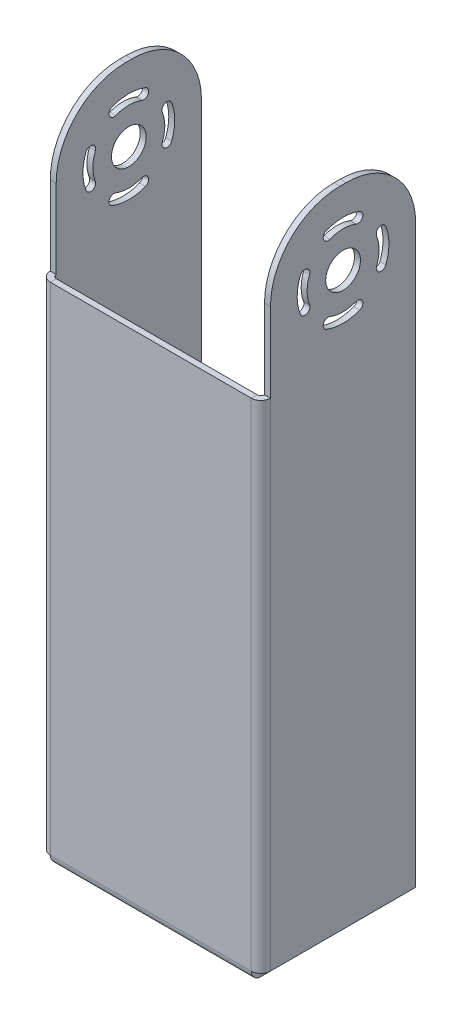
SolidWorks part; units mm, degrees
note: The reader was unsure of these and kept them because the rebuilt part matched: flange length of "邊線-凸緣1", "邊線-凸緣3".
ref_plane "前基準面" through (0, 0, 0) normal (0, 0, 1) x (1, 0, 0)
ref_plane "上基準面" through (0, 0, 0) normal (0, 1, 0) x (1, 0, 0)
ref_plane "右基準面" through (0, 0, 0) normal (1, 0, 0) x (0, 0, -1)
sketch "草圖1" plane through (0, 0, 0) normal (0, 0, 1) x (1, 0, 0)
  line L1 (-49.32, 41.3608) -> (-8.82, 41.3608)
  line L2 (-49.32, 41.3608) -> (-49.32, -58.6392)
  line L3 (-49.32, -58.6392) -> (-8.82, -58.6392)
  line L4 (-8.82, 41.3608) -> (-8.82, -58.6392)
  dimension "D1" = 40.5
  dimension "D2" = 100
base flange "基材-凸緣1" sketch "草圖1" thickness 1.2 reverse thickness direction no parameters "D1"=0.7366
edge flange "邊線-凸緣1" sketch "草圖10" flange profiles "草圖10", "草圖11" flange angle 90 flange length 30 flange position bend outside bend radius 0.7366 thickness 1.2 relief rectangular parameters "D6"=10, "D8"=1
sketch "草圖10" plane through (-8.82, 0, -1.2) normal (-1, 0, 0) x (0, 1, 0)
  line L1 (41.3608, 0) -> (-58.6392, 0) construction
  line L2 (-58.6392, 0) -> (-58.6392, 30)
  line L3 (-58.6392, 30) -> (41.3608, 30)
  line L4 (41.3608, 30) -> (41.3608, 0)
  line L5 (41.3608, 0) -> (-58.6392, 0)
sketch "草圖11" plane through (-49.32, 0, -1.2) normal (1, 0, 0) x (0, -1, 0)
  line L0 (58.6392, 0) -> (-41.3608, 0) construction
  line L1 (58.6392, 0) -> (-41.3608, 0)
  line L2 (58.6392, 0) -> (58.6392, 30)
  line L3 (58.6392, 30) -> (-41.3608, 30)
  line L4 (-41.3608, 30) -> (-41.3608, 0)
bend "邊線彎折7" bend radius 0.7366 bend angle 90 parameters "D5"=1
bend "邊線彎折8" bend radius 0.7366 bend angle 90 parameters "D5"=2
edge flange "邊線-凸緣3" sketch "草圖21" flange angle 90 flange length 20.735 flange position bend outside bend radius 0.7366 thickness 1.2 relief rectangular parameters "D6"=10
sketch "草圖21" plane through (0, -58.6392, -1.2) normal (0, -1, 0) x (-1, 0, 0)
  line L0 (49.32, 0) -> (8.82, 0) construction
  line L1 (49.32, 0) -> (8.82, 0)
  line L2 (8.82, 0) -> (8.82, 20.735)
  line L3 (8.82, 20.735) -> (49.32, 20.735)
  line L4 (49.32, 20.735) -> (49.32, 0)
bend "邊線彎折4" bend radius 0.7366 bend angle 90 parameters "D5"=3
sketch "草圖25" plane through (0, -60.5758, 0) normal (0, -1, 0) x (1, 0, 0)
  line L0 (-29.07, -1.9366) -> (-29.07, -21.935) construction
  line L1 (-49.32, -1.9366) -> (-8.82, -1.9366) construction
  line L2 (-49.32, -11.9358) -> (-8.82, -11.9358) construction
  line L3 (-49.32, -1.9366) -> (-49.32, -21.935) construction
  line L4 (-8.82, -21.935) -> (-8.82, -1.9366) construction
  line L5 (-49.32, -21.935) -> (-8.82, -21.935) construction
  circle A0 centre (-43.58, -6.9366) radius 1.5
  circle A1 centre (-43.58, -16.935) radius 1.5
  circle A2 centre (-14.56, -16.935) radius 1.5
  circle A3 centre (-14.56, -6.9366) radius 1.5
  dimension "D1" = 3
  dimension "D2" = 14.51
  dimension "D3" = 4.9992
  dimension "D4" = 14.51
extrude "除料-伸長1" cut sketch "草圖25" against normal blind 10 normal cut yes
sketch "草圖26" plane through (0, 41.3608, 0) normal (0, 1, 0) x (1, 0, 0)
  line L0 (-51.2566, 31.2) -> (-51.2566, 1.9366) construction
  line L1 (-51.2566, 1.9366) -> (-50.0566, 1.9366) construction
  line L2 (-50.0566, 1.9366) -> (-50.0566, 31.2) construction
  line L3 (-50.0566, 31.2) -> (-51.2566, 31.2) construction
  line L4 (-8.0834, 31.2) -> (-8.0834, 1.9366) construction
  line L5 (-8.0834, 1.9366) -> (-6.8834, 1.9366) construction
  line L6 (-6.8834, 1.9366) -> (-6.8834, 31.2) construction
  line L7 (-6.8834, 31.2) -> (-8.0834, 31.2) construction
  line L8 (-51.2566, 31.2) -> (-51.2566, 1.9366)
  line L9 (-51.2566, 1.9366) -> (-50.0566, 1.9366)
  line L10 (-50.0566, 1.9366) -> (-50.0566, 31.2)
  line L11 (-50.0566, 31.2) -> (-51.2566, 31.2)
  line L12 (-8.0834, 31.2) -> (-8.0834, 1.9366)
  line L13 (-8.0834, 1.9366) -> (-6.8834, 1.9366)
  line L14 (-6.8834, 1.9366) -> (-6.8834, 31.2)
  line L15 (-6.8834, 31.2) -> (-8.0834, 31.2)
extrude "填料-伸長1" add sketch "草圖26" along normal blind 30
sketch "草圖29" plane through (-6.8834, 0, 0) normal (1, 0, 0) x (0, 0, -1)
  line L0 (1.9366, 56.3608) -> (31.2, 56.3608) construction
  line L1 (1.9366, 71.3608) -> (1.9366, 41.3608) construction
  line L2 (31.2, 71.3608) -> (31.2, -58.6392) construction
  line L3 (16.5683, 71.3608) -> (16.5683, 41.3608) construction
  line L4 (1.9366, 71.3608) -> (31.2, 71.3608) construction
  arc A0 (25.1851, 52.9972) -> (25.1851, 59.7244) centre (16.5683, 56.3608) ccw
  arc A1 (25.1851, 59.7244) -> (23.322, 58.9972) centre (24.2535, 59.3608) ccw
  circle A2 centre (16.5683, 56.3608) radius 3.5
  arc A3 (13.2047, 64.9776) -> (13.9319, 63.1145) centre (13.5683, 64.046) ccw
  arc A4 (19.2047, 63.1145) -> (19.9319, 64.9776) centre (19.5683, 64.046) ccw
  arc A5 (19.9319, 64.9776) -> (13.2047, 64.9776) centre (16.5683, 56.3608) ccw
  arc A6 (19.2047, 63.1145) -> (13.9319, 63.1145) centre (16.5683, 56.3608) ccw
  arc A7 (23.322, 53.7244) -> (25.1851, 52.9972) centre (24.2535, 53.3608) ccw
  arc A8 (23.322, 53.7244) -> (23.322, 58.9972) centre (16.5683, 56.3608) ccw
  arc A9 (13.2047, 47.7441) -> (19.9319, 47.7441) centre (16.5683, 56.3608) ccw
  arc A10 (19.9319, 47.7441) -> (19.2047, 49.6071) centre (19.5683, 48.6756) ccw
  arc A11 (13.9319, 49.6071) -> (13.2047, 47.7441) centre (13.5683, 48.6756) ccw
  arc A12 (13.9319, 49.6071) -> (19.2047, 49.6071) centre (16.5683, 56.3608) ccw
  arc A13 (7.9515, 59.7244) -> (7.9515, 52.9972) centre (16.5683, 56.3608) ccw
  arc A14 (7.9515, 52.9972) -> (9.8146, 53.7244) centre (8.8831, 53.3608) ccw
  arc A15 (9.8146, 58.9972) -> (7.9515, 59.7244) centre (8.8831, 59.3608) ccw
  arc A16 (9.8146, 58.9972) -> (9.8146, 53.7244) centre (16.5683, 56.3608) ccw
  point P39 (16.5683, 56.3608)
  dimension "D1" = 4
  dimension "D3" = 7
  dimension "D4" = 2
  dimension "D5" = 2
  dimension "D6" = 6
  dimension "D7" = 3
extrude "除料-伸長2" cut sketch "草圖29" against normal blind 87 normal cut yes
fillet "圓角1" radius 14 4 edges at (-50.6566, 71.3608, -31.2) (-7.4834, 71.3608, -31.2) (-7.4834, 71.3608, -1.9366) (-50.6566, 71.3608, -1.9366)
sketch "彎折-線1" plane through (0, 0, 0) normal (0, 1, 0) x (1, 0, 0)
sketch "邊界方塊1" plane through (0, 0, 0) normal (0, 1, 0) x (1, 0, 0)
sheet metal parameters "鈑金(1)" thickness 1.2 parameters "D1"=0.7366
flat pattern "平板-型式(1)" [suppressed]
sketch "彎折-線2" plane through (0, 0, 0) normal (0, 1, 0) x (1, 0, 0)
sketch "邊界方塊2" [suppressed] plane through (0, 0, 0) normal (0, 1, 0) x (1, 0, 0)
sheet metal parameters "鈑金(2)" thickness 1.2 parameters "D1"=0.7366
flat pattern "平板-型式(1)" [suppressed]
sketch "彎折-線3" plane through (0, 0, 0) normal (0, 1, 0) x (1, 0, 0)
sketch "邊界方塊3" [suppressed] plane through (0, 0, 0) normal (0, 1, 0) x (1, 0, 0)
bend of the flat pattern "平板-<邊線彎折7>1"
bend of the flat pattern "平板-<邊線彎折8>1"
sheet metal parameters "鈑金(4)" thickness 1.2 parameters "D1"=0.7366
flat pattern "平板-型式(1)" [suppressed]
sketch "彎折-線5" plane through (0, 0, 0) normal (0, 1, 0) x (1, 0, 0)
sketch "邊界方塊5" [suppressed] plane through (0, 0, 0) normal (0, 1, 0) x (1, 0, 0)
bend of the flat pattern "平板-<邊線彎折4>1"
bend of the flat pattern "平板-<邊線彎折7>2"
bend of the flat pattern "平板-<邊線彎折8>2"
sheet metal parameters "鈑金(6)" thickness 1.2 parameters "D1"=0.7366
flat pattern "平板-型式(1)" [suppressed]
sketch "彎折-線7" plane through (0, 0, 0) normal (0, 1, 0) x (1, 0, 0)
sketch "邊界方塊7" [suppressed] plane through (0, 0, 0) normal (0, 1, 0) x (1, 0, 0)
bend of the flat pattern "平板-<邊線彎折4>3"
bend of the flat pattern "平板-<邊線彎折7>4"
bend of the flat pattern "平板-<邊線彎折8>4"
sheet metal parameters "鈑金(11)" thickness 1.2 parameters "D1"=0.7366
flat pattern "平板-型式(1)" [suppressed]
sketch "彎折-線8" plane through (0, 0, 0) normal (0, 1, 0) x (1, 0, 0)
sketch "邊界方塊8" [suppressed] plane through (0, 0, 0) normal (0, 1, 0) x (1, 0, 0)
bend of the flat pattern "平板-<邊線彎折4>4"
bend of the flat pattern "平板-<邊線彎折7>5"
bend of the flat pattern "平板-<邊線彎折8>5"
sheet metal parameters "鈑金(12)" thickness 1.2 parameters "D1"=0.7366
flat pattern "平板-型式(1)" [suppressed]
sketch "彎折-線9" plane through (0, 0, 0) normal (0, 1, 0) x (1, 0, 0)
sketch "邊界方塊9" [suppressed] plane through (0, 0, 0) normal (0, 1, 0) x (1, 0, 0)
bend of the flat pattern "平板-<邊線彎折4>5"
bend of the flat pattern "平板-<邊線彎折7>6"
bend of the flat pattern "平板-<邊線彎折8>6"
